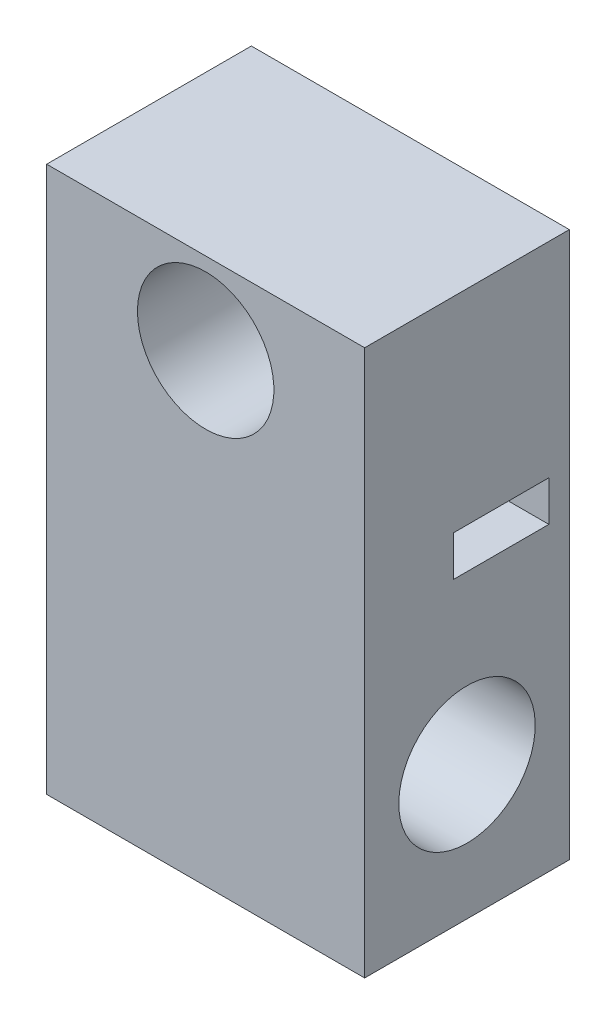
SolidWorks part; units mm, degrees
ref_plane "Front Plane" through (0, 0, 0) normal (0, 0, 1) x (1, 0, 0)
ref_plane "Top Plane" through (0, 0, 0) normal (0, 1, 0) x (1, 0, 0)
ref_plane "Right Plane" through (0, 0, 0) normal (1, 0, 0) x (0, 0, -1)
sketch "Sketch1" plane through (0, 0, 0) normal (0, 0, 1) x (1, 0, 0)
  line L1 (-14.7983, 25.4) -> (14.7983, 25.4)
  line L2 (-14.7983, 25.4) -> (-14.7983, -25.4)
  line L3 (-14.7983, -25.4) -> (14.7983, -25.4)
  line L4 (14.7983, 25.4) -> (14.7983, -25.4)
  line L5 (-14.7983, 25.4) -> (14.7983, -25.4) construction
  line L6 (-14.7983, -25.4) -> (14.7983, 25.4) construction
  circle A0 centre (0, 17.78) radius 6.35
  point P0 (0, 0)
  dimension "D1" = 12.7
  dimension "D2" = 25.4
  dimension "D3" = 7.62
extrude "Boss-Extrude1" add sketch "Sketch1" along normal blind 19.05
sketch "Sketch2" plane through (-14.7983, 0, 0) normal (-1, 0, 0) x (0, 0, 1)
  line L0 (0, 25.4) -> (0, -25.4) construction
  line L1 (1.905, 6.35) -> (10.795, 6.35)
  line L2 (1.905, 6.35) -> (1.905, 2.5919)
  line L3 (1.905, 2.5919) -> (10.795, 2.5919)
  line L4 (10.795, 6.35) -> (10.795, 2.5919)
  line L5 (1.905, 6.35) -> (10.795, 2.5919) construction
  line L6 (1.905, 2.5919) -> (10.795, 6.35) construction
  line L7 (19.05, 25.4) -> (0, 25.4) construction
  point P0 (6.35, 4.471)
  point P7 (0, 0)
  dimension "D1" = 8.89
  dimension "D2" = 6.35
  dimension "D3" = 19.05
extrude "Cut-Extrude1" cut sketch "Sketch2" against normal blind 30.48
sketch "Sketch3" plane through (-14.7983, 0, 0) normal (-1, 0, 0) x (0, 0, 1)
  line L0 (0, 25.4) -> (0, -25.4) construction
  circle A0 centre (9.525, -12.9498) radius 6.35
  dimension "D1" = 12.7
  dimension "D2" = 9.525
extrude "Cut-Extrude2" cut sketch "Sketch3" against normal blind 45.72
